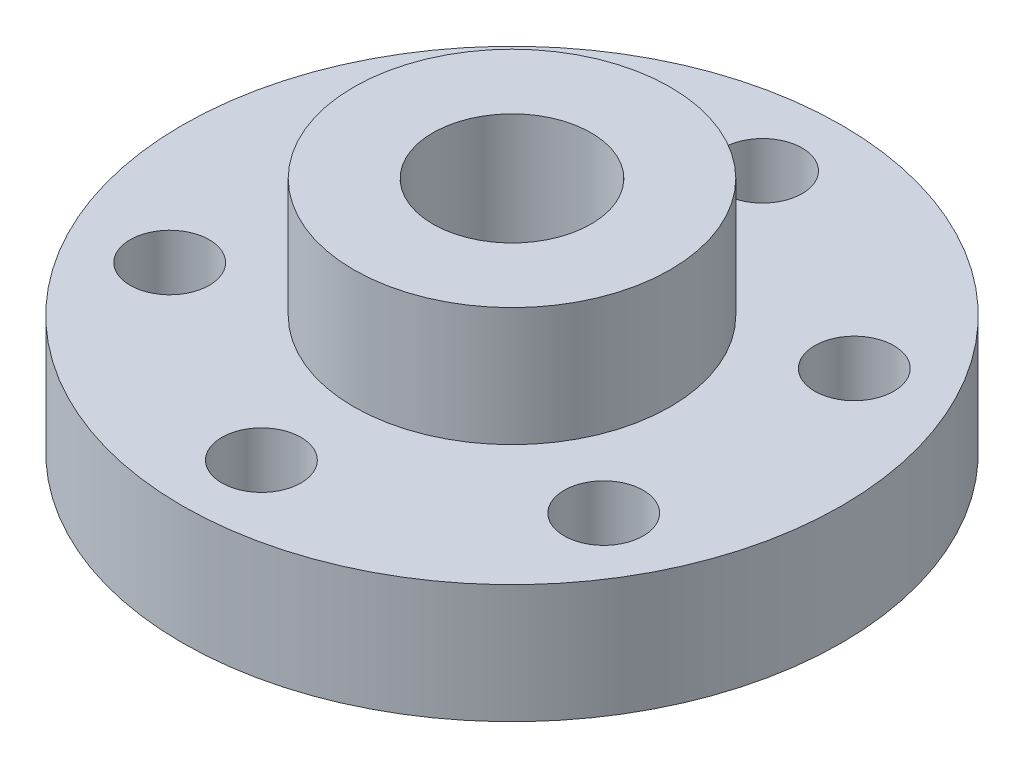
SolidWorks part; units mm, degrees
ref_plane "Front Plane" through (0, 0, 0) normal (0, 0, 1) x (1, 0, 0)
ref_plane "Top Plane" through (0, 0, 0) normal (0, 1, 0) x (1, 0, 0)
ref_plane "Right Plane" through (0, 0, 0) normal (1, 0, 0) x (0, 0, -1)
sketch "Sketch1" plane through (0, 0, 0) normal (0, 1, 0) x (1, 0, 0)
  circle A0 centre (0, 0) radius 3
  circle A1 centre (0, 9.5) radius 1.5
  circle A2 centre (0, 0) radius 12.5
  circle A3 centre (8.2272, 4.75) radius 1.5
  circle A4 centre (8.2272, -4.75) radius 1.5
  circle A5 centre (0, -9.5) radius 1.5
  circle A6 centre (-8.2272, -4.75) radius 1.5
  circle A7 centre (-8.2272, 4.75) radius 1.5
  circle A8 centre (0, 0) radius 6
  point P18 (0, 0)
  dimension "D1" = 6
  dimension "D3" = 3
  dimension "D4" = 25
  dimension "D6" = 3
  dimension "D2" = 9.5
  dimension "D5" = 6
extrude "Boss-Extrude1" add sketch "Sketch1" along normal blind 4.5 contours A8 A0 | A2 A8 A7 A6 A5 A4 A3 A1 region at (-12.1464, 0, 0) region at (-5.8303, 0, 0)
extrude "Boss-Extrude2" add sketch "Sketch1<3>" along normal blind 4.5 from surface contours A8 A0 region at (-5.8303, 0, 0) starting at face at (0, 4.5, 3)
sketch "Sketch1<3>" plane through (0, 0, 0) normal (0, 1, 0) x (1, 0, 0) same geometry as "Sketch1"
